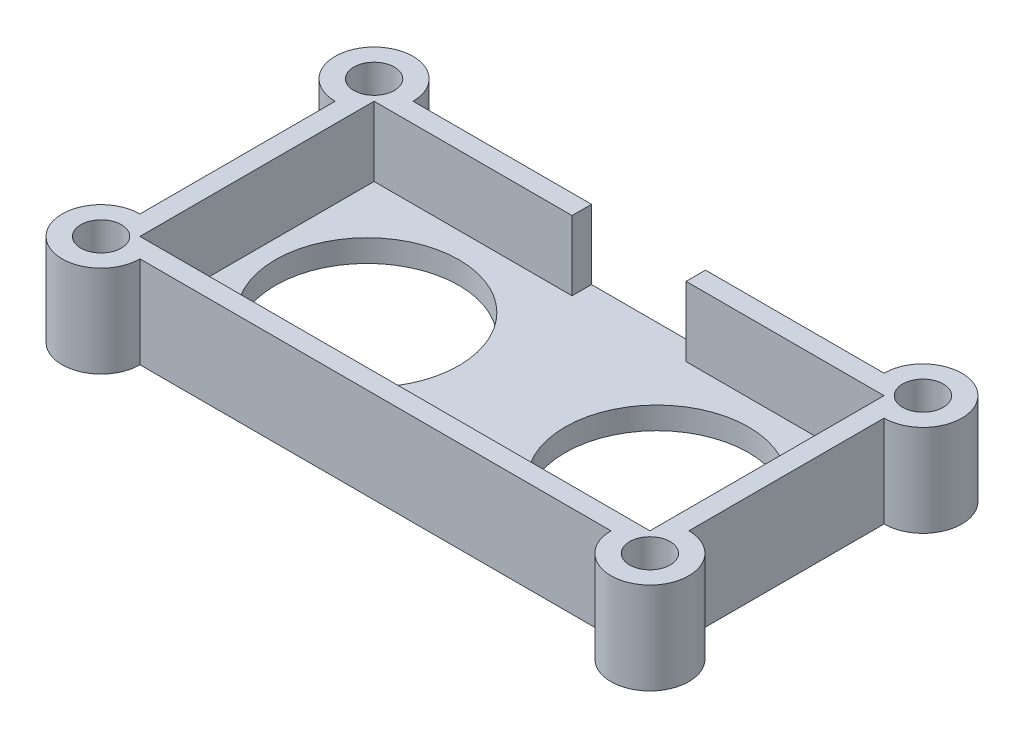
SolidWorks part; units mm, degrees
ref_plane "Front Plane" through (0, 0, 0) normal (0, 0, 1) x (1, 0, 0)
ref_plane "Top Plane" through (0, 0, 0) normal (0, 1, 0) x (1, 0, 0)
ref_plane "Right Plane" through (0, 0, 0) normal (1, 0, 0) x (0, 0, -1)
sketch "Sketch1" plane through (0, 0, 0) normal (0, 1, 0) x (1, 0, 0)
  line L1 (-24.675, 12.275) -> (24.675, 12.275)
  line L2 (-24.675, 12.275) -> (-24.675, -12.275)
  line L3 (-24.675, -12.275) -> (24.675, -12.275)
  line L4 (24.675, 12.275) -> (24.675, -12.275)
  dimension "D1" = 49.35
  dimension "D2" = 24.675
  dimension "D3" = 24.55
  dimension "D4" = 12.275
extrude "Boss-Extrude1" add sketch "Sketch1" along normal blind 2
sketch "Sketch2" plane through (0, 2, 0) normal (0, 1, 0) x (1, 0, 0)
  line L0 (-24.675, 12.275) -> (-24.675, -12.275)
  line L1 (-24.675, -12.275) -> (24.675, -12.275)
  line L2 (24.675, -12.275) -> (24.675, 12.275)
  line L3 (24.675, 12.275) -> (5.125, 12.275)
  line L4 (24.675, 12.275) -> (-24.675, 12.275) construction
  line L5 (5.125, 12.275) -> (5.125, 10.525)
  line L6 (5.125, 10.525) -> (22.925, 10.525)
  line L7 (22.925, 10.525) -> (22.925, -10.525)
  line L8 (22.925, -10.525) -> (-22.925, -10.525)
  line L9 (-22.925, -10.525) -> (-22.925, 10.525)
  line L10 (-22.925, 10.525) -> (-5.125, 10.525)
  line L11 (-5.125, 10.525) -> (-5.125, 12.275)
  line L12 (-5.125, 12.275) -> (-24.675, 12.275)
  dimension "D1" = 19.55
  dimension "D2" = 1.75
  dimension "D3" = 1.75
  dimension "D4" = 1.75
  dimension "D5" = 1.75
  dimension "D6" = 1.75
  dimension "D7" = 19.55
extrude "Boss-Extrude2" add sketch "Sketch2" along normal blind 6.25
sketch "Sketch4" plane through (0, 2, 0) normal (0, 1, 0) x (1, 0, 0)
  line L0 (-24.675, 12.275) -> (-24.675, 8.775)
  line L1 (-24.675, 12.275) -> (-21.175, 12.275)
  line L2 (-24.675, -12.275) -> (-24.675, -8.775)
  line L3 (-24.675, -12.275) -> (-21.175, -12.275)
  line L4 (24.675, -12.275) -> (21.175, -12.275)
  line L5 (24.675, -12.275) -> (24.675, -8.775)
  line L6 (24.675, 8.775) -> (24.675, 12.275)
  line L7 (24.675, 12.275) -> (21.175, 12.275)
  arc A0 (-21.175, 12.275) -> (-24.675, 8.775) centre (-24.675, 12.275) ccw
  arc A1 (-24.675, -8.775) -> (-21.175, -12.275) centre (-24.675, -12.275) ccw
  arc A2 (21.175, -12.275) -> (24.675, -8.775) centre (24.675, -12.275) ccw
  arc A3 (24.675, 8.775) -> (21.175, 12.275) centre (24.675, 12.275) ccw
  dimension "D1" = 7
  dimension "D2" = 7
  dimension "D3" = 7
  dimension "D4" = 7
extrude "Boss-Extrude3" add sketch "Sketch4" along normal up to surface (6.25 mm away) and the other way up to surface (2 mm away) up to face at (0, 8.25, -3.8) other way up to face at (0, 0, 0)
sketch "Sketch3" plane through (0, 2, 0) normal (0, 1, 0) x (1, 0, 0)
  line L0 (-3, -7.35) -> (3.25, -7.35) construction
  line L1 (-3, -4.975) -> (3.25, -4.975)
  line L2 (-3, -9.725) -> (3.25, -9.725)
  line L5 (-22.925, -10.525) -> (-22.925, 10.525) construction
  line L7 (22.925, 10.525) -> (22.925, -10.525) construction
  line L9 (22.925, -10.525) -> (-22.925, -10.525) construction
  line L11 (22.925, -10.525) -> (-22.925, -10.525) construction
  line L12 (-22.925, -10.525) -> (-22.925, 10.525) construction
  circle A0 centre (-13.025, 0) radius 8.25
  circle A1 centre (13.025, 0) radius 8.25
  arc A2 (-3, -4.975) -> (-3, -9.725) centre (-3, -7.35) ccw
  arc A3 (3.25, -9.725) -> (3.25, -4.975) centre (3.25, -7.35) ccw
  circle A4 centre (-24.675, 12.275) radius 1.825
  circle A5 centre (-24.675, -12.275) radius 1.825
  circle A6 centre (24.675, 12.275) radius 1.825
  circle A7 centre (24.675, -12.275) radius 1.825
  point P6 (0.125, -7.35)
  point P16 (-22.925, 0)
  point P18 (22.925, 0)
  point P23 (-5.375, -7.35)
  point P24 (5.625, -7.35)
  dimension "D1" = 16.5
  dimension "D2" = 16.5
  dimension "D11" = 3.65
  dimension "D12" = 3.65
  dimension "D13" = 3.65
  dimension "D14" = 3.65
  dimension "D3" = 9.9
  dimension "D4" = 9.9
  dimension "D5" = 10.525
  dimension "D6" = 10.525
  dimension "D7" = 4.75
  dimension "D8" = 0.8
  dimension "D9" = 11
  dimension "D10" = 17.55
extrude "Cut-Extrude1" cut sketch "Sketch3" against normal through all and the other way through all
